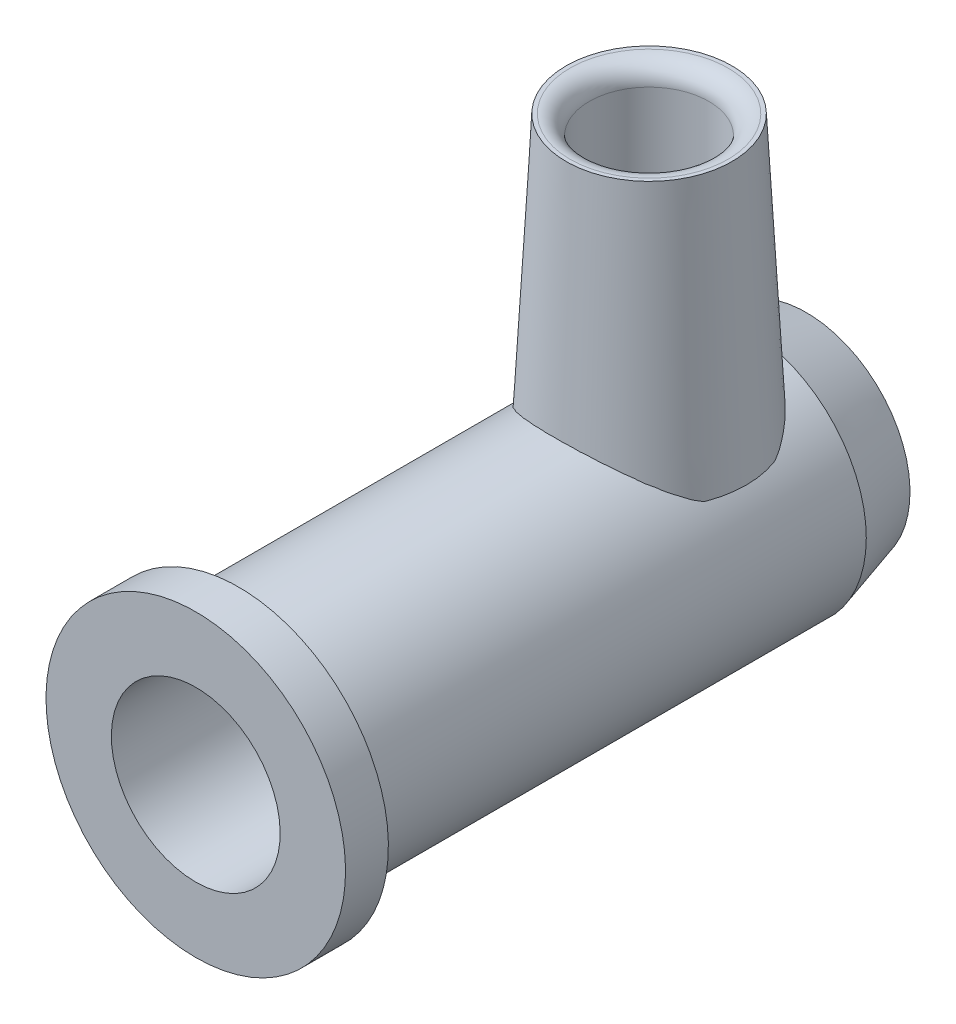
SolidWorks part; units mm, degrees
ref_plane "Front Plane" through (0, 0, 0) normal (1, 0, 0) x (0, 1, 0)
ref_plane "Top Plane" through (0, 0, 0) normal (0, 0, 1) x (0, 1, 0)
ref_plane "Right Plane" through (0, 0, 0) normal (0, 1, 0) x (-1, 0, 0)
sketch "Sketch1" plane through (0, 0, 0) normal (1, 0, 0) x (0, 1, 0)
  line L0 (10.9855, 23.6827) -> (13.4255, 23.6827)
  line L1 (10.9855, 23.6827) -> (10.9855, 22.0827)
  line L2 (10.9855, 22.0827) -> (12.0349, 22.0827)
  line L3 (12.0349, 22.0827) -> (12.0349, 3.1947)
  line L4 (12.0349, 3.1947) -> (12.7055, 0.8927)
  line L5 (12.7055, 0.8927) -> (13.4255, 0.8927)
  line L6 (13.4255, 0.8927) -> (13.4255, 23.6827)
  line L7 (16.5755, 25.7651) -> (16.5755, -2.8132) construction
  dimension "D1" = 22.79
  dimension "D2" = 18.888
  dimension "D3" = 5.59
  dimension "D4" = 1.6
  dimension "D5" = 2.44
  dimension "D7" = 0.72
revolve "Revolve1" add sketch "Sketch1" angle 360 about L7
sketch "Sketch6" plane through (0, 0, 0.8927) normal (0, 0, -1) x (1, 0, 0)
  line L0 (0, -16.5755) -> (3.2107, -19.7863)
  line L1 (3.2107, -19.7863) -> (0, -21.1162)
  line L2 (0, -21.1162) -> (0, -16.5755)
  circle A0 centre (0, -16.5755) radius 4.5407 construction
  circle A1 centre (0, -16.5755) radius 4.5407 construction
ref_plane "Plane2" through (0, 21.1162, 0.8927) normal (0, 1, 0) x (1, 0, 0)
sketch "Sketch7" plane through (0, 21.1162, 0.8927) normal (0, 1, 0) x (1, 0, 0)
  line L0 (0, 0) -> (0, -5.87)
  circle A0 centre (0, -5.87) radius 3.552
  circle A1 centre (0, -5.87) radius 2.2317
  circle A2 centre (0, -5.87) radius 1.54
  point P8 (0, -5.87)
  dimension "D2" = 3.08
  dimension "D3" = 4.4633
  dimension "D4" = 7.104
  dimension "D1" = 5.87
extrude "Boss-Extrude1" add sketch "Sketch7" against normal blind 1 contours A2 A1 region at (1.5334, 21.1162, 5.2293)
extrude "Cut-Extrude1" cut sketch "Sketch7<4>" against normal blind 8.5 contours A2 region at (1.0581, 21.1162, 5.7045)
sketch "Sketch7<4>" plane through (0, 21.1162, 0.8927) normal (0, 1, 0) x (1, 0, 0) same geometry as "Sketch7"
sketch "Sketch12" plane through (0, 21.1162, 0) normal (0, 1, 0) x (-1, 0, 0)
  circle A0 centre (0, 6.7627) radius 2.2316
  circle A1 centre (0, 6.7627) radius 3.045
  dimension "D1" = 6.09
extrude "Boss-Extrude2" add sketch "Sketch12" along normal blind 8.69 separate body
sketch "Sketch13" plane through (0, 21.1162, 0.8927) normal (0, 1, 0) x (1, 0, 0)
  circle A0 centre (0, -5.87) radius 3.552
  circle A1 centre (0, -5.87) radius 2.9502
ref_plane "Plane3" through (0, 29.8062, 0) normal (0, 1, 0) x (1, 0, 0)
sketch "Sketch14" plane through (0, 29.8062, 0) normal (0, 1, 0) x (1, 0, 0)
  circle A0 centre (0, -6.7627) radius 2.9502
sketch "Sketch7<9>" plane through (0, 21.1162, 0.8927) normal (0, 1, 0) x (1, 0, 0) same geometry as "Sketch7"
sketch "Sketch7<10>" plane through (0, 21.1162, 0.8927) normal (0, 1, 0) x (1, 0, 0) same geometry as "Sketch7"
sketch "Sketch15" plane through (0, 21.1162, 0.8927) normal (0, 1, 0) x (1, 0, 0)
  circle A0 centre (0, -5.87) radius 3.552
  circle A1 centre (0, -5.87) radius 2.2317
sketch "Sketch16" plane through (0, 29.8062, 0) normal (0, 1, 0) x (1, 0, 0)
  circle A0 centre (0, -6.7627) radius 2.9501
sketch "Sketch17" plane through (0, 0, 23.6827) normal (0, 0, 1) x (1, 0, 0)
  circle A0 centre (0, 16.5755) radius 3.15
  circle A1 centre (0, 16.5755) radius 2.055
  dimension "D1" = 4.11
extrude "Boss-Extrude4" add sketch "Sketch15" along normal blind 8.69 draft 3 and the other way blind 1.5 draft 3 other way draft outward yes
fillet "Fillet2" radius 0.7185 1 edges at (0, 29.8062, 8.9943)
sketch "Sketch19" plane through (0, 0, 23.6827) normal (0, 0, 1) x (1, 0, 0)
  circle A0 centre (0, 16.5755) radius 2.055
  circle A1 centre (0, 16.5755) radius 3.15
